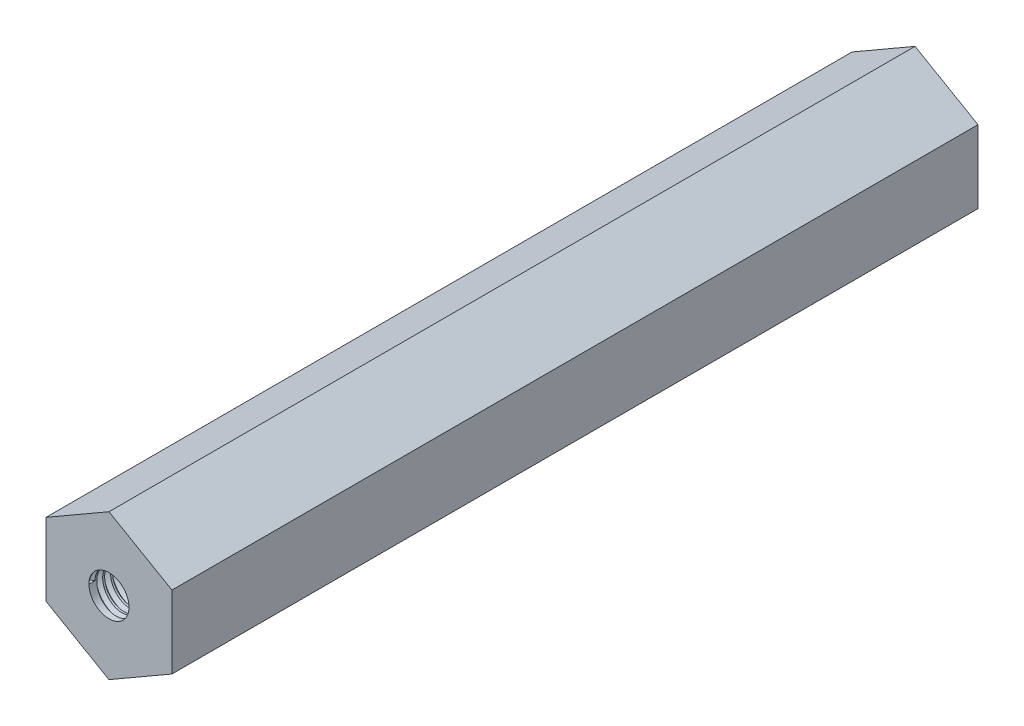
SolidWorks part; units mm, degrees
other "Markup1"
sketch "Sketch3" plane through (6.35, 7.3323, -19.05) normal (0.3384, 0.0641, -0.9388) x (-0.9259, -0.1556, -0.3443)
material "7075-T6 (SN)"
ref_plane "Front Plane" through (0, 0, 0) normal (0, 0, 1) x (1, 0, 0)
ref_plane "Top Plane" through (0, 0, 0) normal (0, 1, 0) x (1, 0, 0)
ref_plane "Right Plane" through (0, 0, 0) normal (1, 0, 0) x (0, 0, -1)
sketch "Sketch1" plane through (0, 0, 0) normal (0, 0, 1) x (1, 0, 0)
  line L1 (0, 7.3323) -> (-6.35, 3.6662)
  line L2 (-6.35, 3.6662) -> (-6.35, -3.6662)
  line L3 (-6.35, -3.6662) -> (0, -7.3323)
  line L4 (0, -7.3323) -> (6.35, -3.6662)
  line L5 (6.35, -3.6662) -> (6.35, 3.6662)
  line L6 (6.35, 3.6662) -> (0, 7.3323)
  circle A0 centre (0, 0) radius 6.35 construction
  dimension "D1" = 12.7
extrude "Boss-Extrude1" add sketch "Sketch1" along normal mid plane 81.28
sketch "Sketch2" plane through (0, 0, -40.64) normal (0, 0, -1) x (-1, 0, 0)
  circle A0 centre (0, 0) radius 2.0193
  dimension "D1" = 4.0386
extrude "Cut-Extrude1" cut sketch "Sketch2" against normal through all
thread "Thread2" pitch 0.7937 method cut profile "Thread Profile2" start angle 0, offset 0, length 12.7, pitch 0.7937, diameter 4.0386
ref_plane "Plane2" through (2.0193, 0, -40.64) normal (0, -1, 0) x (1, 0, 0)
sketch "Thread Profile2" plane through (2.0193, 0, -40.64) normal (0, -1, 0) x (1, 0, 0)
  line L0 (0, 0) -> (0, 0.7937) construction
  line L1 (0, 0) -> (0.4296, 0.248)
  line L2 (0.4296, 0.248) -> (0.4296, 0.3473)
  line L3 (0.4296, 0.3473) -> (0, 0.5953)
  line L4 (0.4296, 0.2977) -> (0, 0.2977) construction
  line L11 (0, 0) -> (0, 0.5953)
  point P2 (0, 0)
  dimension "Pitch" = 0.7937
  dimension "Profile_Angle" = 60
  dimension "Profile_Land" = 0.0992
  dimension "Profile_Height" = 0.4296
thread "Thread3" pitch 0.7937 method cut profile "Thread Profile3" start angle 0, offset 0, length 12.7, pitch 0.7937, diameter 4.0386
ref_plane "Plane3" through (-2.0193, 0, 40.64) normal (0, -1, 0) x (-1, 0, 0)
sketch "Thread Profile3" plane through (-2.0193, 0, 40.64) normal (0, -1, 0) x (-1, 0, 0)
  line L0 (0, 0) -> (0, 0.7937) construction
  line L1 (0, 0) -> (0.4296, 0.248)
  line L2 (0.4296, 0.248) -> (0.4296, 0.3473)
  line L3 (0.4296, 0.3473) -> (0, 0.5953)
  line L4 (0.4296, 0.2977) -> (0, 0.2977) construction
  line L11 (0, 0) -> (0, 0.5953)
  point P2 (0, 0)
  dimension "Pitch" = 0.7937
  dimension "Profile_Angle" = 60
  dimension "Profile_Land" = 0.0992
  dimension "Profile_Height" = 0.4296
